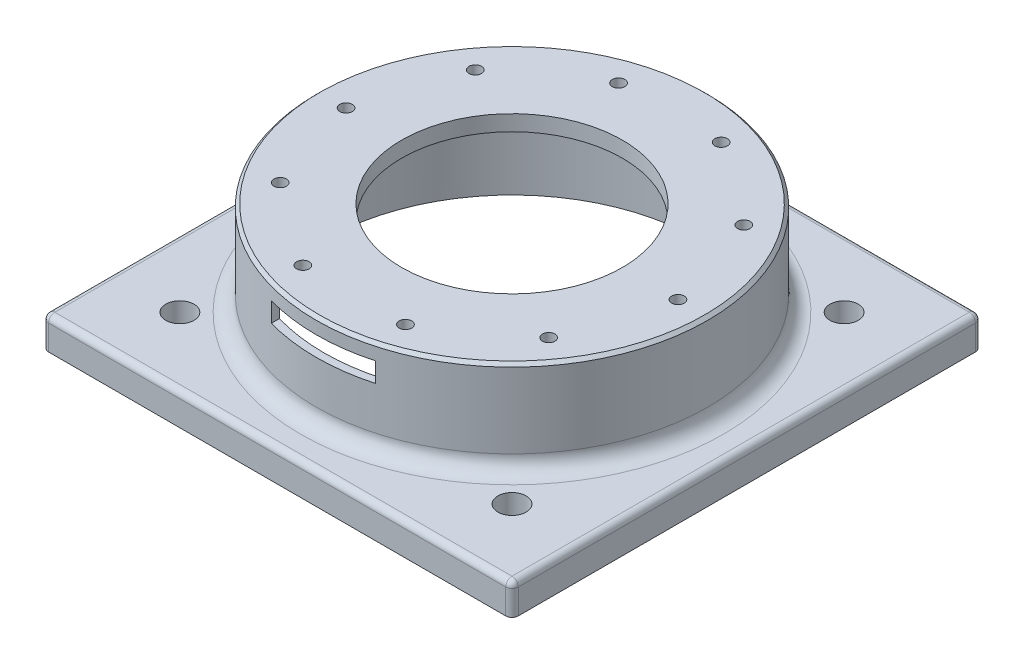
SolidWorks part; units mm, degrees
ref_plane "Спереди" through (0, 0, 0) normal (0, 0, 1) x (1, 0, 0)
ref_plane "Сверху" through (0, 0, 0) normal (0, 1, 0) x (1, 0, 0)
ref_plane "Справа" through (0, 0, 0) normal (1, 0, 0) x (0, 0, -1)
sketch "Эскиз1" plane through (0, 0, 0) normal (0, 1, 0) x (1, 0, 0)
  line L0 (0, 0) -> (53.033, 53.033) construction
  line L5 (75, -75) -> (-75, -75)
  line L6 (75, -75) -> (75, 75)
  line L7 (75, 75) -> (-75, 75)
  line L8 (-75, -75) -> (-75, 75)
  line L9 (75, -75) -> (-75, 75) construction
  line L10 (75, 75) -> (-75, -75) construction
  circle A2 centre (0, 0) radius 75 construction
  circle A3 centre (53.033, 53.033) radius 4.5
  circle A4 centre (0, 0) radius 75 construction
  circle A5 centre (53.033, -53.033) radius 4.5
  circle A6 centre (0, 0) radius 75 construction
  circle A7 centre (-53.033, -53.033) radius 4.5
  circle A8 centre (0, 0) radius 75 construction
  circle A9 centre (-53.033, 53.033) radius 4.5
  point P0 (0, 0)
  dimension "D3" = 150
  dimension "D4" = 9
  dimension "D1" = 150
  dimension "D2" = 150
  dimension "D5" = 4
extrude "Бобышка-Вытянуть1" add sketch "Эскиз1" along normal blind 10
fillet "Скругление1" radius 2 4 edges at (-75, 5, -75) (75, 5, -75) (-75, 5, 75) (75, 5, 75)
fillet "Скругление2" radius 2 8 edges at (-74.4142, 10, -74.4142) (74.4142, 10, -74.4142) (74.4142, 10, 74.4142) (-74.4142, 10, 74.4142) (0, 10, 75) (75, 10, 0) (0, 10, -75) (-75, 10, 0)
sketch "Эскиз4" plane through (0, 10, 0) normal (0, 1, 0) x (1, 0, 0)
  circle A0 centre (0, 0) radius 62.5
  dimension "D1" = 125
extrude "Бобышка-Вытянуть4" add sketch "Эскиз4" along normal blind 30 contours A0
fillet "Скругление5" radius 5 1 edges at (0, 10, 62.5)
sketch "Эскиз10" plane through (0, 0, 0) normal (0, -1, 0) x (1, 0, 0)
  circle A0 centre (0, 0) radius 60
  dimension "D1" = 120
sketch "Эскиз3" plane through (0, 10, 0) normal (0, 1, 0) x (1, 0, 0)
  line L0 (0, -75) -> (0, 75)
  line L1 (-73, 75) -> (73, 75) construction
  circle A1 centre (-53.033, 53.033) radius 6.25
  circle A2 centre (-53.033, -53.033) radius 6.25
  circle A3 centre (53.033, -53.033) radius 6.25
  circle A4 centre (53.033, 53.033) radius 6.25
  point P14 (0, 0)
  dimension "D2" = 12.5
  dimension "D3" = 12.5
  dimension "D1" = 150
extrude "Вырез-Вытянуть1" [suppressed] cut sketch "Эскиз3" along normal up to next contours A3 | A2 | A1 | A4
sketch "Эскиз11" plane through (0, 40, 0) normal (0, 1, 0) x (1, 0, 0)
  circle A0 centre (0, 0) radius 35.25
  dimension "D1" = 70.5
extrude "Вырез-Вытянуть2" cut sketch "Эскиз11" against normal through all contours A0
extrude "Вырез-Вытянуть3" cut sketch "Эскиз10" against normal blind 35 contours A0
sketch "Эскиз12" plane through (0, 40, 0) normal (0, 1, 0) x (1, 0, 0)
  line L0 (0, 0) -> (-53, 0) construction
  circle A0 centre (0, 0) radius 53 construction
  circle A1 centre (-53, 0) radius 2
  circle A2 centre (0, 0) radius 53
  circle A3 centre (0, 0) radius 35.25 construction
  circle A4 centre (-42.8779, 31.1526) radius 2
  circle A5 centre (0, 0) radius 53
  circle A6 centre (-16.3779, 50.406) radius 2
  circle A7 centre (0, 0) radius 53
  circle A8 centre (16.3779, 50.406) radius 2
  circle A9 centre (0, 0) radius 53
  circle A10 centre (42.8779, 31.1526) radius 2
  circle A11 centre (0, 0) radius 53
  circle A12 centre (53, 0) radius 2
  circle A13 centre (0, 0) radius 53
  circle A14 centre (42.8779, -31.1526) radius 2
  circle A15 centre (0, 0) radius 53
  circle A16 centre (16.3779, -50.406) radius 2
  circle A17 centre (0, 0) radius 53
  circle A18 centre (-16.3779, -50.406) radius 2
  circle A19 centre (0, 0) radius 53
  circle A20 centre (-42.8779, -31.1526) radius 2
  dimension "D2" = 4
  dimension "D3" = 53
  dimension "D5" = 53
  dimension "D4" = 10
extrude "Вырез-Вытянуть4" cut sketch "Эскиз12" against normal through all contours A4 | A1 | A20 | A18 | A16 | A14 | A12 | A10 | A8 | A6
chamfer "Фаска2" distance 1 angle 45 1 edges at (0, 40, 62.5)
ref_plane "Смещенная плоскость для разъема" through (0, 0, 62.5) normal (0, 0, 1) x (1, 0, 0)
sketch "Эскиз14" plane through (0, 0, 62.5) normal (0, 0, 1) x (1, 0, 0)
  line L0 (61.5, 40) -> (-61.5, 40) construction
  line L1 (16.625, 28.75) -> (-16.625, 28.75)
  line L2 (16.625, 28.75) -> (16.625, 35)
  line L3 (16.625, 35) -> (-16.625, 35)
  line L4 (-16.625, 28.75) -> (-16.625, 35)
  line L5 (16.625, 28.75) -> (-16.625, 35) construction
  line L6 (16.625, 35) -> (-16.625, 28.75) construction
  line L7 (-62.5, 39) -> (-62.5, 15) construction
  point P0 (0, 31.875)
  dimension "D1" = 33.25
  dimension "D2" = 6.25
  dimension "D3" = 5
  dimension "D4" = 45.875
extrude "Вырез-Вытянуть5" cut sketch "Эскиз14" against normal blind 5
equation "\"D2@Эскиз1\"=\"D1@Эскиз1\""
equation "\"D3@Эскиз1\"=\"D1@Эскиз1\""
equation "\"D3@Эскиз3\"=\"D2@Эскиз3\""
